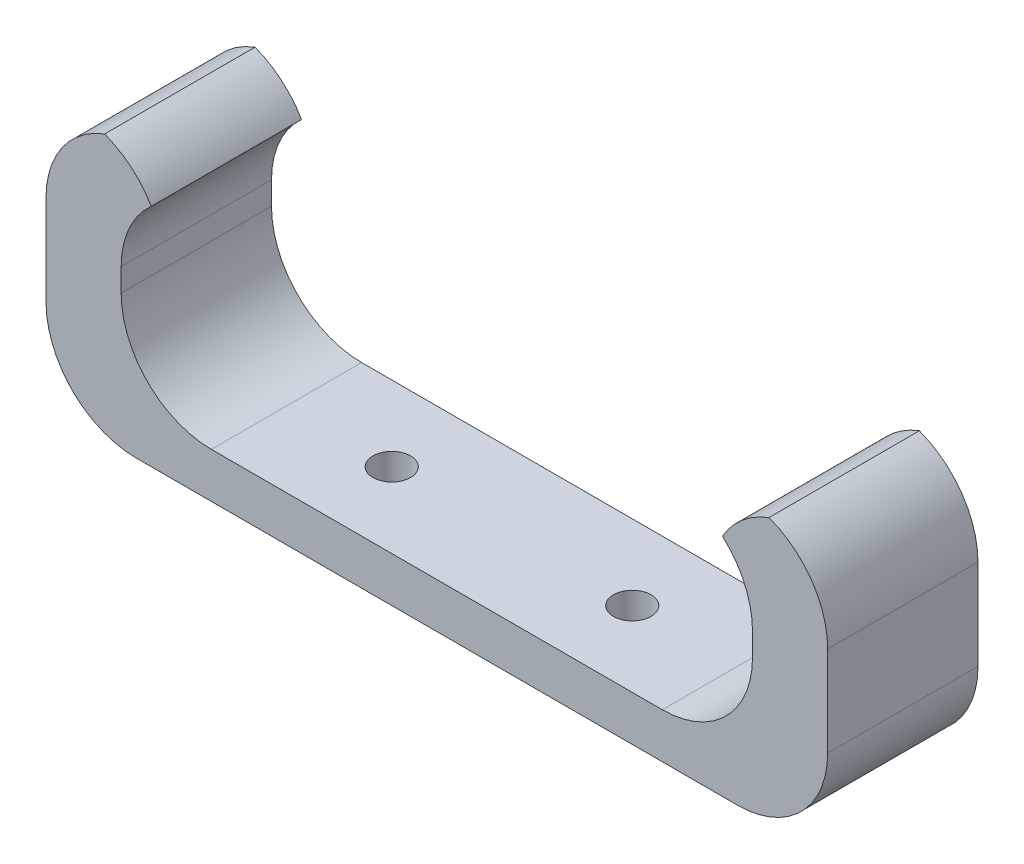
SolidWorks part; units mm, degrees
ref_plane "Front Plane" through (0, 0, 0) normal (0, 0, 1) x (1, 0, 0)
ref_plane "Top Plane" through (0, 0, 0) normal (0, 1, 0) x (1, 0, 0)
ref_plane "Right Plane" through (0, 0, 0) normal (1, 0, 0) x (0, 0, -1)
sketch "Sketch1" plane through (0, 0, 0) normal (0, 1, 0) x (1, 0, 0)
  line L0 (0, 0) -> (16, 0)
  line L2 (-13, -5) -> (29, -5)
  line L3 (-13, -5) -> (-13, 5)
  line L4 (-13, 5) -> (29, 5)
  line L5 (29, -5) -> (29, 5)
  line L6 (-13, -5) -> (29, 5) construction
  line L7 (-13, 5) -> (29, -5) construction
  circle A0 centre (0, 0) radius 1.25
  circle A1 centre (16, 0) radius 1.25
  point P5 (8, 0)
  dimension "D2" = 2.5
  dimension "D3" = 2.5
  dimension "D1" = 16
  dimension "D4" = 42
  dimension "D5" = 10
extrude "Boss-Extrude1" add sketch "Sketch1" along normal blind 3 contours L2 L5 L4 L3 A1 A0 region at (-12.5683, 0, 0)
sketch "Sketch2" plane through (0, 0, 0) normal (0, -1, 0) x (1, 0, 0)
  line L0 (-13, 5) -> (-13, -5)
  line L1 (-13, 5) -> (-18, 5)
  line L2 (-13, -5) -> (-18, -5)
  line L3 (-18, 5) -> (-18, -5)
  line L4 (29, 5) -> (29, -5)
  line L5 (29, 5) -> (34, 5)
  line L6 (29, -5) -> (34, -5)
  line L7 (34, 5) -> (34, -5)
  dimension "D1" = 5
  dimension "D2" = 5
extrude "Boss-Extrude2" add sketch "Sketch2" against normal blind 18
sketch "Sketch3" plane through (-13, 0, 0) normal (1, 0, 0) x (0, 0, -1)
  line L0 (-5, 18) -> (5, 18)
  line L1 (-5, 18) -> (-5, 15)
  line L2 (5, 18) -> (5, 15)
  line L3 (-5, 15) -> (5, 15)
  dimension "D1" = 3
extrude "Boss-Extrude3" add sketch "Sketch3" along normal blind 2
sketch "Sketch4" plane through (29, 0, 0) normal (-1, 0, 0) x (0, 0, 1)
  line L0 (-5, 18) -> (5, 18)
  line L1 (-5, 18) -> (-5, 15)
  line L2 (5, 18) -> (5, 15)
  line L3 (-5, 15) -> (5, 15)
  dimension "D1" = 3
extrude "Boss-Extrude4" add sketch "Sketch4" along normal blind 2
fillet "Fillet1" radius 6 10 edges at (29, 15, 0) (29, 3, 0) (-13, 15, 0) (-13, 3, 0) (-18, 0, 0) (34, 0, 0) (34, 18, 0) (-18, 18, 0) (27, 18, 0) (-11, 18, 0)
